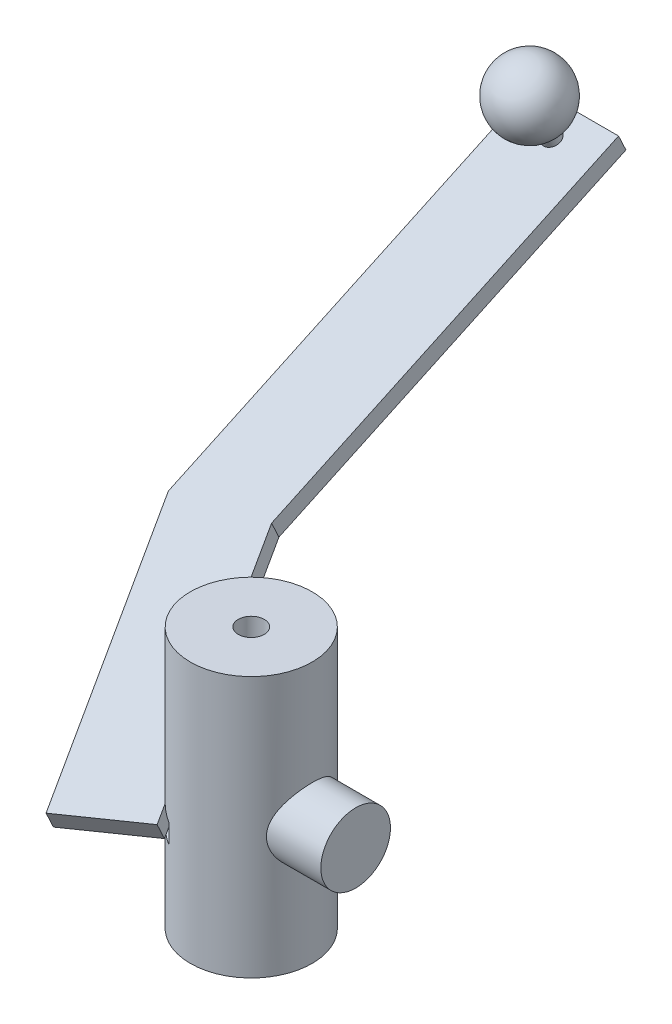
SolidWorks part; units mm, degrees
ref_plane "Front Plane" through (0, 0, 0) normal (0, 0, 1) x (1, 0, 0)
ref_plane "Top Plane" through (0, 0, 0) normal (0, 1, 0) x (1, 0, 0)
ref_plane "Right Plane" through (0, 0, 0) normal (1, 0, 0) x (0, 0, -1)
sketch "Sketch1" plane through (0, 0, 0) normal (0, 1, 0) x (1, 0, 0)
  circle A0 centre (0, 0) radius 22.225
  circle A1 centre (0, 0) radius 4.7625
  dimension "D1" = 44.45
  dimension "D2" = 9.525
extrude "Boss-Extrude1" add sketch "Sketch1" along normal blind 95.25
sketch "Sketch2" plane through (0, 0, 0) normal (1, 0, 0) x (0, 0, -1)
  line L0 (0, 44.45) -> (0, 95.25) construction
  line L1 (4.7625, 95.25) -> (-4.7625, 95.25) construction
  circle A0 centre (0, 44.45) radius 12.7
  dimension "D1" = 25.4
  dimension "D2" = 50.8
extrude "Boss-Extrude2" add sketch "Sketch2" along normal blind 38.1
sketch "Sketch3" plane through (0, 0, 0) normal (1, 0, 0) x (0, 0, -1)
  line L0 (-34.4336, 31.1551) -> (-31.75, 25.4)
  line L1 (-34.4336, 31.1551) -> (184.2584, 133.1328)
  line L2 (-31.75, 25.4) -> (186.9421, 127.3778)
  line L3 (184.2584, 133.1328) -> (186.9421, 127.3778)
  line L4 (-22.225, 0) -> (22.225, 0) construction
  dimension "D1" = 25
  dimension "D2" = 6.35
  dimension "D3" = 25.4
  dimension "D4" = 241.3
  dimension "D5" = 9.525
extrude "Boss-Extrude3" add sketch "Sketch3" against normal blind 101.6 from offset 10.16 offset against normal yes
sketch "Sketch4" plane through (0, 38.7794, 18.0831) normal (0, 0.9063, 0.4226) x (1, 0, 0)
  line L0 (-81.9804, 77.0434) -> (-41.9646, -16.3444)
  line L1 (-81.9804, 223.2592) -> (-50.2304, 223.2592)
  line L2 (-81.9804, 223.2592) -> (-81.9804, 77.0434)
  line L3 (-41.9646, -16.3444) -> (-12.7809, -3.8395)
  line L4 (-50.2304, 223.2592) -> (-50.2304, 83.5592)
  line L5 (-10.16, 41.7627) -> (-10.16, 223.2592)
  line L6 (-10.16, 223.2592) -> (-111.76, 223.2592)
  line L7 (-111.76, 223.2592) -> (-111.76, -18.0408)
  line L8 (-111.76, -18.0408) -> (-10.16, -18.0408)
  line L9 (-10.16, -18.0408) -> (-10.16, -1.8577)
  line L10 (-10.16, 223.2592) -> (-10.16, -18.0408)
  line L11 (-10.16, 223.2592) -> (-111.76, 223.2592)
  line L12 (-111.76, 223.2592) -> (-111.76, -18.0408)
  line L13 (-111.76, -18.0408) -> (-10.16, -18.0408)
  line L14 (-111.76, 223.2592) -> (-10.16, 223.2592) construction
  line L15 (-12.7809, -3.8395) -> (-50.2304, 83.5592)
  line L16 (-81.9804, 77.0434) -> (-50.2304, 83.5592) construction
  line L17 (-66.1054, 80.3013) -> (-66.1054, 223.2592) construction
  line L18 (-66.1054, 80.3013) -> (-27.3727, -10.092) construction
  ellipse E1 centre (0, 19.9525) end of major axis (0, -4.57) minor radius 22.225 (-10.16, 41.7627) -> (-10.16, -1.8577) ccw
  ellipse M7 centre (0, 19.9525) end of major axis (0, -4.57) minor radius 22.225 (-10.16, -1.8577) -> (-10.16, 41.7627) cw
  line M8 (-10.16, 41.7627) -> (-10.16, 223.2592)
  line M9 (-10.16, 223.2592) -> (-111.76, 223.2592)
  line M10 (-111.76, 223.2592) -> (-111.76, -18.0408)
  line M11 (-111.76, -18.0408) -> (-10.16, -18.0408)
  line M12 (-10.16, -18.0408) -> (-10.16, -1.8577)
  dimension "D2" = 31.75
  dimension "D3" = 31.75
  dimension "D4" = 139.7
  dimension "D5" = 101.6
  dimension "D1" = 0
extrude "Cut-Extrude1" cut sketch "Sketch4" against normal blind 6.35 contours L15 L3 L0 L2 M9 M10 M11 M12 M7 | L15 L4 M7 M8 M9 region at (-88.7538, 72.9489, -55.1936) region at (-29.2555, 95.3651, -103.2653)
sketch "Sketch5" plane through (0, 38.7794, 18.0831) normal (0, 0.9063, 0.4226) x (1, 0, 0)
  line L0 (-66.1054, 223.2592) -> (-66.1054, 213.7342) construction
  line L1 (-81.9804, 223.2592) -> (-50.2304, 223.2592) construction
  circle A0 centre (-66.1054, 213.7342) radius 3.175
  dimension "D1" = 6.35
  dimension "D2" = 9.525
extrude "Boss-Extrude4" add sketch "Sketch5" along normal blind 6.35
dome "Dome1" faces to dome 1 distance 25.4 reverse direction no elliptical dome no face at (-66.1054, 133.5206, -170.0647) parameters "D1"=25.4
